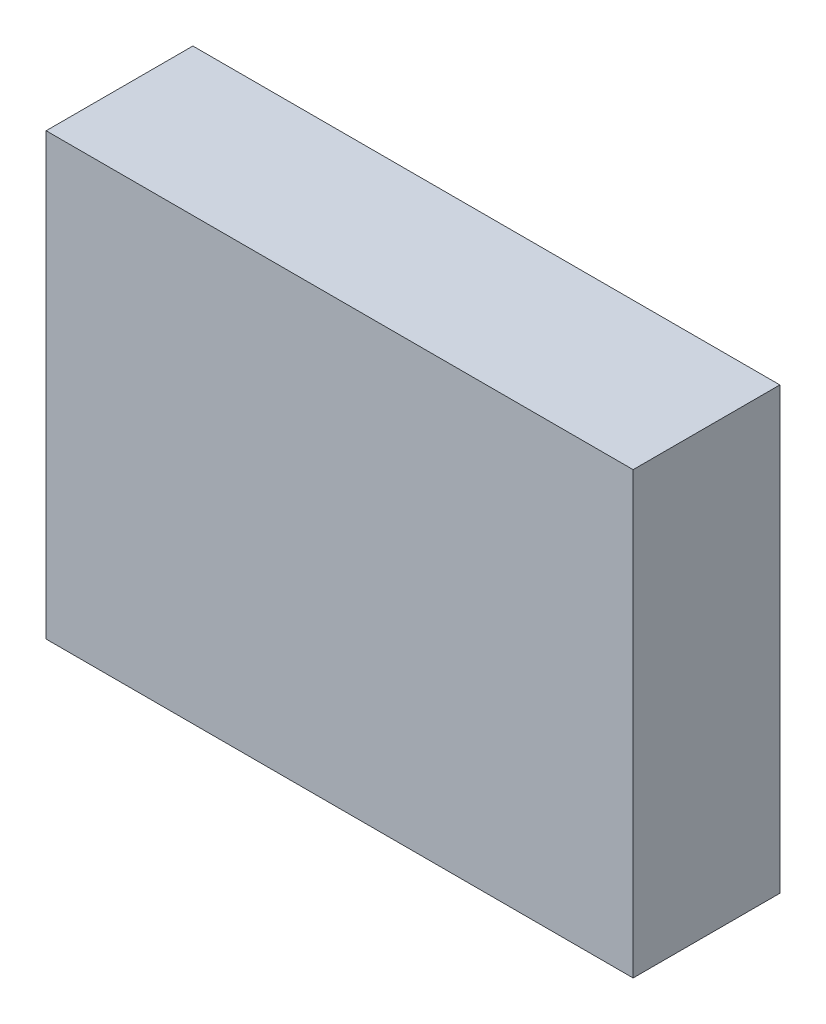
SolidWorks part; units mm, degrees
material "Cast Alloy Steel"
ref_plane "Front Plane" through (0, 0, 0) normal (1, 0, 0) x (0, 1, 0)
ref_plane "Top Plane" through (0, 0, 0) normal (0, 0, 1) x (0, 1, 0)
ref_plane "Right Plane" through (0, 0, 0) normal (0, 1, 0) x (-1, 0, 0)
sketch "Sketch1" plane through (0, 0, 0) normal (1, 0, 0) x (0, 1, 0)
  line L1 (0, -55) -> (0, 55) construction
  line L2 (-90, 30) -> (0, 30)
  line L3 (-90, 30) -> (-90, 0)
  line L4 (-90, 0) -> (0, 0)
  line L5 (0, 30) -> (0, 0)
  line L6 (0, 30) -> (150, 30)
  line L7 (0, 30) -> (0, 1030)
  line L8 (0, 1030) -> (150, 1030)
  line L9 (150, 30) -> (150, 1030)
  line L10 (-90, 0) -> (-240, 0)
  line L11 (-90, 0) -> (-90, -500)
  line L12 (-90, -500) -> (-240, -500)
  line L13 (-240, 0) -> (-240, -500)
  line L14 (55, 0) -> (-55, 0) construction
  dimension "D1" = 1000
  dimension "D2" = 150
  dimension "D3" = 150
  dimension "D4" = 30
  dimension "D5" = 90
  dimension "D6" = 500
  dimension "D7" = 0
  dimension "D8" = 0
extrude "Boss-Extrude2" add sketch "Sketch1" along normal blind 60 and the other way blind 60 contours L5 L2 L3 L4 region at (0, -45, 15)
sketch "Sketch2" plane through (0, 0, 0) normal (0, 0, -1) x (1, 0, 0)
  line L1 (-7.5, 29) -> (7.5, 29)
  line L2 (-7.5, 29) -> (-7.5, 61)
  line L3 (-7.5, 61) -> (7.5, 61)
  line L4 (-60, 0) -> (60, 0)
  line L5 (60, 0) -> (60, 90)
  line L6 (60, 90) -> (-60, 90)
  line L7 (-60, 90) -> (-60, 0)
  line L8 (-60, 0) -> (60, 0)
  line L9 (60, 0) -> (60, 90)
  line L10 (60, 90) -> (-60, 90)
  line L11 (-60, 90) -> (-60, 0)
  line L12 (7.5, 29) -> (7.5, 61)
  point P8 (0, 90)
  point P9 (0, 29)
  point P10 (-7.5, 45)
  point P11 (-60, 45)
  point P13 (-7.5, 61)
  point P14 (-7.5, 29)
  point P15 (7.5, 61)
  point P16 (7.5, 29)
  dimension "D2" = 0
  dimension "D3" = 0
  dimension "D4" = 15
  dimension "D5" = 32
  dimension "D1" = 0
hole_wizard "Ø2.0mm Dowel Hole1" positions "Sketch2" profile "Sketch4" hole size "Ø2.0" standard "IS"
sketch "Sketch4" plane through (7.5, -29, 0) normal (1, 0, 0) x (0, 1, 0)
  line L0 (0, 0) -> (0, 10.6009)
  line L1 (0, 10.6009) -> (1, 10)
  line L2 (1, 10) -> (1, 0.025)
  line L3 (1, 0.025) -> (1.025, 0)
  line L5 (1.025, 0) -> (0, 0)
  line L6 (-1, 0.025) -> (-1.025, 0) construction
  line L10 (0, 10.6009) -> (-1, 10) construction
  line L11 (0, -6.35) -> (0, 107.95) construction
  dimension "Hole Dia." = 2
  dimension "Hole Depth" = 10
  dimension "Near C'Sink Dia." = 2.05
  dimension "Near C'Sink Angle" = 90
  dimension "Drill Angle" = 118
sketch "Sketch5" plane through (0, 0, 0) normal (0, 0, -1) x (1, 0, 0)
  line L1 (-3, 17.5) -> (3, 17.5)
  line L2 (-3, 17.5) -> (-3, 2.5)
  line L3 (-3, 2.5) -> (3, 2.5)
  line L4 (-60, 0) -> (60, 0)
  line L5 (60, 0) -> (60, 90)
  line L6 (60, 90) -> (-60, 90)
  line L7 (-60, 90) -> (-60, 0)
  line L8 (-60, 0) -> (60, 0)
  line L9 (60, 0) -> (60, 90)
  line L10 (60, 90) -> (-60, 90)
  line L11 (-60, 90) -> (-60, 0)
  line L12 (3, 17.5) -> (3, 2.5)
  point P8 (0, 17.5)
  point P9 (0, 90)
  point P10 (3, 10)
  point P11 (60, 45)
  point P13 (-3, 17.5)
  point P14 (3, 17.5)
  point P15 (3, 2.5)
  point P16 (-3, 2.5)
  dimension "D2" = 0
  dimension "D3" = 6
  dimension "D4" = 15
  dimension "D5" = 35
  dimension "D1" = 0
hole_wizard "Ø2.0mm Dowel Hole2" positions "Sketch5" profile "Sketch6" hole size "Ø2.0" standard "IS"
sketch "Sketch6" plane through (-3, -2.5, 0) normal (1, 0, 0) x (0, 1, 0)
  line L0 (0, 0) -> (0, 10.6009)
  line L1 (0, 10.6009) -> (1, 10)
  line L2 (1, 10) -> (1, 0.025)
  line L3 (1, 0.025) -> (1.025, 0)
  line L5 (1.025, 0) -> (0, 0)
  line L6 (-1, 0.025) -> (-1.025, 0) construction
  line L10 (0, 10.6009) -> (-1, 10) construction
  line L11 (0, -6.35) -> (0, 107.95) construction
  dimension "Hole Dia." = 2
  dimension "Hole Depth" = 10
  dimension "Near C'Sink Dia." = 2.05
  dimension "Near C'Sink Angle" = 90
  dimension "Drill Angle" = 118
